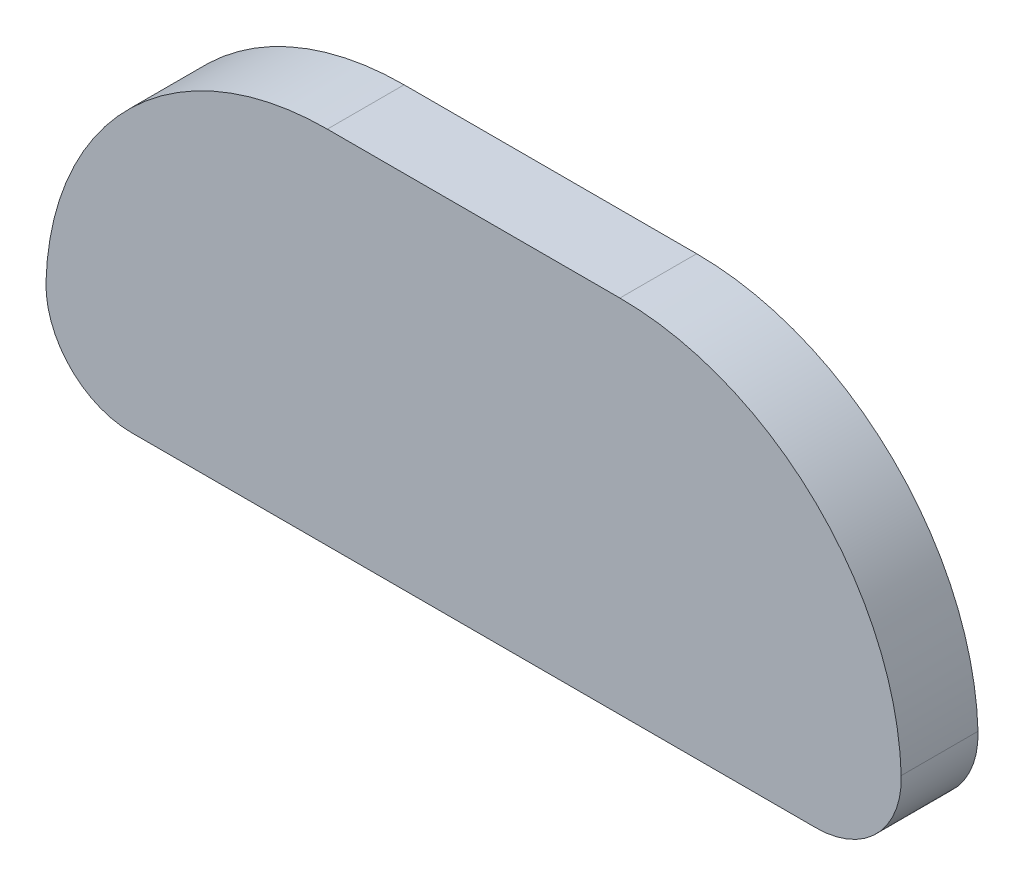
SolidWorks part; units mm, degrees
ref_plane "Plano frontal" through (0, 0, 0) normal (0, 0, 1) x (1, 0, 0)
ref_plane "Plano superior" through (0, 0, 0) normal (0, 1, 0) x (1, 0, 0)
ref_plane "Plano direito" through (0, 0, 0) normal (1, 0, 0) x (0, 0, -1)
sketch "Esboço1" plane through (0, 0, 0) normal (0, 0, 1) x (1, 0, 0)
  line L0 (-39.9126, -26.5911) -> (40.0874, -26.5911) construction
  line L5 (-19.1243, 10.7089) -> (50.2374, -28.131) construction
  line L6 (-50.0626, -27.9516) -> (19.1801, 10.7089) construction
  line L9 (-39.9126, -26.5911) -> (-39.9126, -31.5911) construction
  line L16 (0.0874, 10.7089) -> (0.0874, -31.5911) construction
  line L17 (-50.0626, -31.5911) -> (50.2374, -31.5911)
  line L22 (-45.0626, -21.4411) -> (-50.0626, -21.4411) construction
  line L32 (-50.0626, 10.7089) -> (-50.0626, -31.5911)
  line L35 (45.2374, -21.4411) -> (50.2374, -21.4411) construction
  line L44 (50.2374, 10.7089) -> (50.2374, -31.5911)
  line L45 (-16.5086, 8.7089) -> (-16.5086, 10.7089) construction
  line L61 (-50.0626, -16.68) -> (50.2374, -16.68) construction
  line L80 (-50.0626, 10.7089) -> (50.2374, 10.7089)
  line L82 (-16.5086, -1.5911) -> (16.4914, -1.5911) construction
  circle A7 centre (-16.5086, 3.5589) radius 5.15
  circle A8 centre (16.4914, 3.5589) radius 5.15
  circle A17 centre (-39.9126, -21.4411) radius 5.15
  circle A18 centre (40.0874, -21.4411) radius 5.15
  point P0 (0, 0)
  dimension "D6" = 10.3
  dimension "D9" = 2
  dimension "D7" = 10.3
  dimension "D1" = 5
  dimension "D2" = 5
  dimension "D3" = 5
extrude "Ressalto-extrusão1" add sketch "Esboço1" along normal blind 7
extrude "Ressalto-extrusão2" add sketch "Esboço1<6>" along normal blind 2 from surface contours A7 | A8 | A17 | A18 | L80 L32 L17 L44 A8 A7 A17 A18 region at (0.0915, -10.569, 0) region at (-16.5086, 3.5589, 0) region at (16.4914, 3.5589, 0) region at (-39.9126, -21.4411, 0) region at (40.0874, -21.4411, 0) starting at face at (21.6414, 3.5589, 7)
sketch "Esboço1<6>" plane through (0, 0, 0) normal (0, 0, 1) x (1, 0, 0) same geometry as "Esboço1"
fillet "Filete1" radius 33 2 edges at (50.2374, 10.7089, 4.5) (-50.0626, 10.7089, 4.5)
fillet "Filete2" radius 10 2 edges at (50.2374, -31.5911, 4.5) (-50.0626, -31.5911, 4.5)
